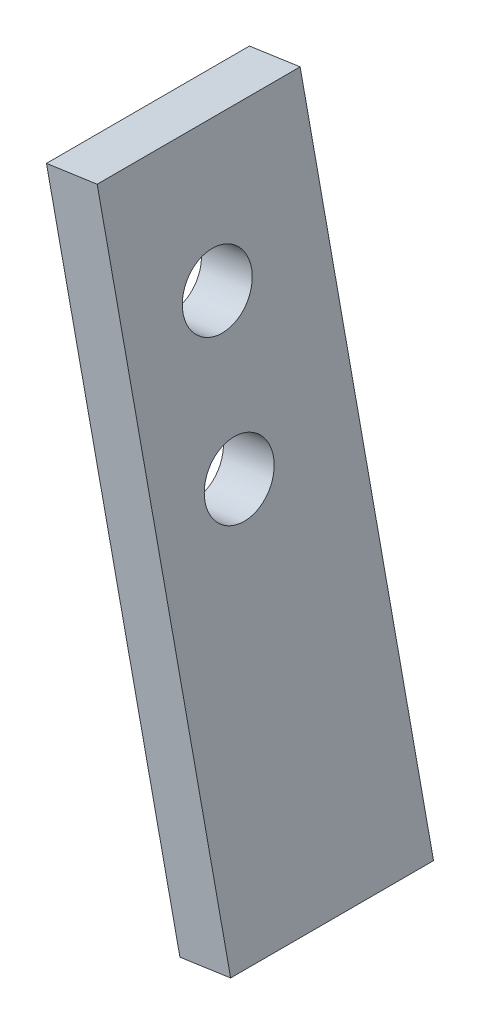
SolidWorks part; units mm, degrees
ref_plane "Front" through (0, 0, 0) normal (0, 0, 1) x (1, 0, 0)
ref_plane "Top" through (0, 0, 0) normal (0, 1, 0) x (1, 0, 0)
ref_plane "Right" through (0, 0, 0) normal (1, 0, 0) x (0, 0, -1)
ref_axis "Axis1" through (38.6204, -344.4414, 4.2776) along (-1, 0, 0)
ref_axis "Axis2" through (40.331, -22.98, 75.0619) along (-0.9898, -0.1426, 0)
ref_axis "Axis3" through (38.1486, -8.1395, 75.0619) along (-0.9898, -0.1426, 0)
ref_point "Point1"
ref_plane "Plane3" through (-15.2153, -2.5724, 84.9119) normal (-0.9898, -0.1426, 0) x (0, 0, 1)
sketch "Sketch2" plane through (-15.2153, -2.5724, 84.9119) normal (-0.9898, -0.1426, 0) x (0, 0, 1)
  line L0 (0, 0) -> (-19.8107, 0.0127)
  line L1 (-19.8107, 0.0127) -> (-23.557, -64.9849)
  line L2 (-23.557, -64.9849) -> (-3.7522, -64.9976)
  line L3 (-19.8107, 0.0127) -> (0, 0) construction
  line L4 (-19.8107, 0.0127) -> (-24.3108, -78.0635) construction
  line L5 (-4.5039, -78.0202) -> (0, 0) construction
  line L6 (-9.85, -13.1219) -> (-9.85, -28.1219) construction
  line L7 (-3.7522, -64.9976) -> (0, 0)
  circle A2 centre (-9.85, -13.1219) radius 3.3779 construction
  circle A3 centre (-9.85, -28.1219) radius 3.3779 construction
  circle A4 centre (-9.85, -13.1219) radius 3.3779
  circle A5 centre (-9.85, -28.1219) radius 3.3779
  dimension "D2" = 6.7558
  dimension "D3" = 6.7558
  dimension "D1" = 65
extrude "Boss-Extrude1" add sketch "Sketch2" against normal blind 5
sketch3d "3DSketch1"
  line L0 (-5.9451, -66.8991, 71.2573) -> (-0.9962, -66.1859, 71.2573)
  line L1 (-5.946, -66.8929, 61.3549) -> (-5.9442, -66.9054, 81.1597) construction
  line L2 (-0.9971, -66.1797, 61.3549) -> (-0.9953, -66.1922, 81.1597) construction
  line L3 (-0.9962, -66.1859, 71.2573) -> (39.5846, -60.3378, 71.2573)
  line L4 (39.5846, -60.3378, 71.2573) -> (0, -60.3378, 71.2573) construction
  line L5 (0, -60.3378, 71.2573) -> (0, -395.047, 71.2573) construction
  line L6 (0, -60.3378, 71.2573) -> (0, -395.047, 0) construction
  line L8 (0, 0, 0) -> (0, -395.047, 0) construction
  line L9 (0, -395.047, 0) -> (49.27, -395.047, 0) construction
  line L11 (0, -395.047, 71.2573) -> (0, -395.047, 0) construction
  line L13 (58.5691, -395.1788, 0) -> (39.5846, -60.3378, 71.2573) construction
  point P16 (58.5691, -395.1788, 0)
  dimension "D1" = 41
  dimension "D2" = 12.018
equation "\"D3@Sketch2\"=\"D2@Sketch2\""
